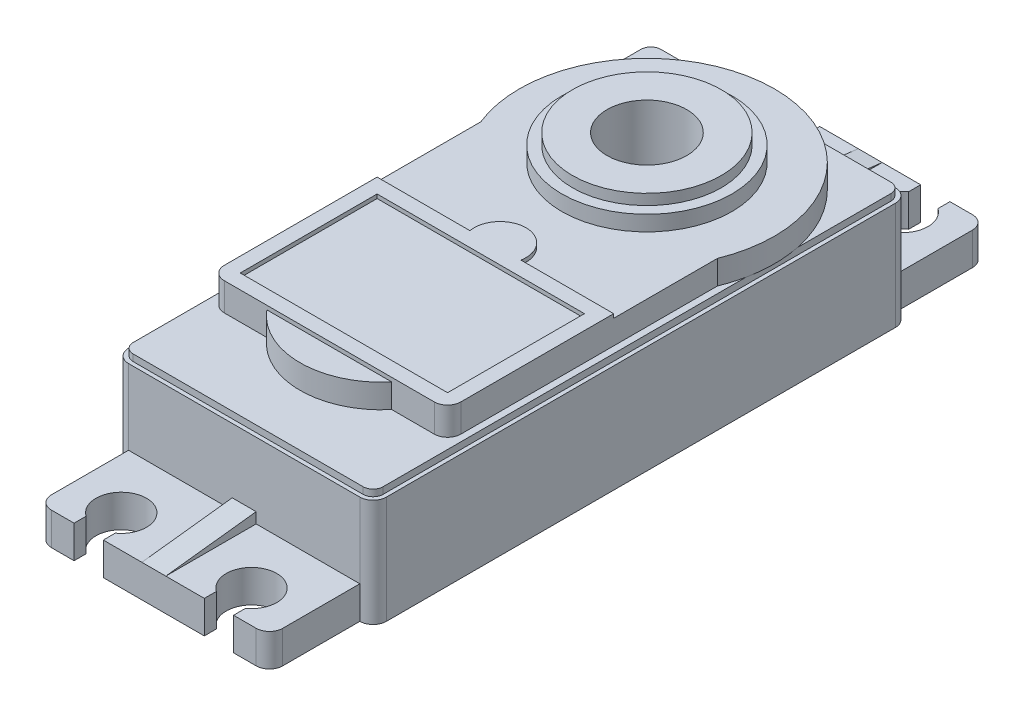
SolidWorks part; units mm, degrees
material "PC High Viscosity"
ref_plane "Front Plane" through (0, 0, 0) normal (0, 0, 1) x (1, 0, 0)
ref_plane "Top Plane" through (0, 0, 0) normal (0, 1, 0) x (1, 0, 0)
ref_plane "Right Plane" through (0, 0, 0) normal (1, 0, 0) x (0, 0, -1)
sketch "BaseS" plane through (0, 0, 0) normal (0, 1, 0) x (1, 0, 0)
  line L1 (-9.7, 20.15) -> (9.7, 20.15)
  line L2 (-9.7, 20.15) -> (-9.7, -20.15)
  line L3 (-9.7, -20.15) -> (9.7, -20.15)
  line L4 (9.7, 20.15) -> (9.7, -20.15)
  line L5 (-9.7, 20.15) -> (9.7, -20.15) construction
  line L6 (-9.7, -20.15) -> (9.7, 20.15) construction
  point P0 (0, 0)
  dimension "D1" = 19.4
  dimension "D2" = 40.3
extrude "BASE" add sketch "BaseS" along normal blind 8.6 contours L4 L3 L2 L1
sketch "ShaftHoleS" plane through (0, 8.6, 0) normal (0, 1, 0) x (1, 0, 0)
  line L0 (0, 10.15) -> (0, 20.15) construction
  line L1 (-9.7, 20.15) -> (9.7, 20.15) construction
  circle A0 centre (0, 10.15) radius 3
  dimension "D1" = 6
  dimension "D2" = 10
extrude "SHAFT HOLE" cut sketch "ShaftHoleS" against normal through all
sketch "MountingTabS" plane through (0, 0, 20.15) normal (0, 0, 1) x (1, 0, 0)
  line L0 (-9.7, 0) -> (9.7, 0) construction
  line L1 (-8.7, 2.45) -> (8.7, 2.45)
  line L2 (-8.7, 2.45) -> (-8.7, 0)
  line L3 (-8.7, 0) -> (8.7, 0)
  line L4 (8.7, 2.45) -> (8.7, 0)
  line L5 (-8.7, 2.45) -> (8.7, 0) construction
  line L6 (-8.7, 0) -> (8.7, 2.45) construction
  line L7 (9.7, 8.6) -> (9.7, 0) construction
  point P0 (0, 1.225)
  dimension "D1" = 1
  dimension "D2" = 2.45
  dimension "D3" = 17.4
extrude "MOUNTING TAB" add sketch "MountingTabS" along normal blind 6.8
sketch "MountingHoleS" plane through (0, 2.45, 0) normal (0, 1, 0) x (1, 0, 0)
  line L0 (0, -26.95) -> (0, -20.15) construction
  line L1 (-6, -26.0492) -> (-6, -26.95)
  line L2 (-6, -26.95) -> (-3.8, -26.95)
  line L3 (-3.8, -26.95) -> (-3.8, -26.0492)
  line L4 (-4.9, -24.5) -> (-4.9, -26.95) construction
  line L5 (8.7, -20.15) -> (-8.7, -20.15) construction
  line L6 (8.7, -26.95) -> (-8.7, -26.95) construction
  line L8 (-9.7, 20.15) -> (-9.7, -20.15) construction
  arc A0 (-3.8, -26.0492) -> (-6, -26.0492) centre (-4.9, -24.5) ccw
  point P16 (-9.7, 0)
  dimension "D1" = 3.8
  dimension "D2" = 4.9
  dimension "D3" = 2.2
  dimension "D4" = 24.5
extrude "MOUNTING HOLE" cut sketch "MountingHoleS" against normal through all
mirror "MH M" about plane through (0, 0, 0) normal (1, 0, 0) of "MOUNTING HOLE"
sketch "BottomAlignHoleS" plane through (0, 0, 0) normal (0, -1, 0) x (1, 0, 0)
  line L0 (0, 26.95) -> (0, 24.95) construction
  line L1 (-3.8, 26.95) -> (3.8, 26.95) construction
  circle A0 centre (0, 24.95) radius 0.7
  dimension "D1" = 1.4
  dimension "D2" = 2
extrude "BOTTOM ALIGN HOLE" cut sketch "BottomAlignHoleS" against normal blind 0.5
sketch "TriangularTabS" plane through (0, 0, 0) normal (1, 0, 0) x (0, 0, -1)
  line L0 (-20.15, 2.45) -> (-26.95, 2.45)
  line L1 (-26.95, 2.45) -> (-20.15, 3.25)
  line L2 (-20.15, 3.25) -> (-20.15, 2.45)
  line L3 (-26.0492, 2.45) -> (-26.95, 2.45) construction
  dimension "D1" = 0.8
extrude "TRIANGULAR TAB" add sketch "TriangularTabS" along normal mid plane 1.8
mirror "MOUNTING TAB FEATURES M" about plane through (0, 0, 0) normal (0, 0, 1) of "TRIANGULAR TAB", "BOTTOM ALIGN HOLE", "MH M", "MOUNTING HOLE", "MOUNTING TAB"
sketch "BaseTopBodyS" plane through (0, 8.6, 0) normal (0, 1, 0) x (1, 0, 0)
  line L0 (-8.9, -13.7486) -> (8.9, -13.7486)
  line L1 (8.9, -13.7486) -> (8.9, 6.5514)
  line L2 (-8.9, -13.7486) -> (-8.9, 6.5514)
  line L3 (0, -13.7486) -> (0, 0) construction
  arc A0 (8.9, 6.5514) -> (-8.9, 6.5514) centre (0, 10.15) ccw
  circle A1 centre (0, 10.15) radius 3
  circle A2 centre (0, 10.15) radius 3 construction
  dimension "D1" = 19.2
  dimension "D2" = 17.8
  dimension "D3" = 20.3
extrude "BASE TOP BODY" add sketch "BaseTopBodyS" along normal blind 1.8
sketch "PartCircleS" plane through (0, 8.6, 0) normal (0, 1, 0) x (1, 0, 0)
  line L0 (-4.7, -13.7486) -> (4.7, -13.7486) construction
  line L1 (0, -13.7486) -> (0, -15.9486) construction
  line L2 (-4.7, -13.7486) -> (4.7, -13.7486)
  line L3 (-8.9, -13.7486) -> (8.9, -13.7486) construction
  arc A0 (-4.7, -13.7486) -> (4.7, -13.7486) centre (0, -9.8282) ccw
  dimension "D1" = 2.2
  dimension "D2" = 9.4
extrude "PART CIRCLE" add sketch "PartCircleS" along normal up to surface (1.8 mm away) up to face at (0, 10.4, 0.299)
sketch "TopBodyCylinder1" plane through (0, 10.4, 0) normal (0, 1, 0) x (1, 0, 0)
  circle A0 centre (0, 10.15) radius 3
  circle A1 centre (0, 10.15) radius 6.4
  circle A2 centre (0, 10.15) radius 3 construction
  dimension "D1" = 12.8
extrude "TOP BODY CYLINDER 1" add sketch "TopBodyCylinder1" along normal blind 1.15
sketch "TopBodyCylinder2" plane through (0, 11.55, 0) normal (0, 1, 0) x (1, 0, 0)
  circle A0 centre (0, 10.15) radius 5.6
  circle A1 centre (0, 10.15) radius 6.4 construction
  circle A2 centre (0, 10.15) radius 3 construction
  circle A3 centre (0, 10.15) radius 3
  dimension "D1" = 0.8
  dimension "D2" = 11.2
extrude "TOB BODY CYLINDER 2" add sketch "TopBodyCylinder2" along normal blind 0.8
sketch "TopBodyLabelNest" plane through (0, 10.4, 0) normal (0, 1, 0) x (1, 0, 0)
  line L0 (-8.9, -1.2486) -> (8.9, -1.2486)
  line L1 (-8.9, -1.2486) -> (-8.9, -13.7486)
  line L2 (-8.9, -13.7486) -> (8.9, -13.7486)
  line L3 (8.9, -1.2486) -> (8.9, -13.7486)
  line L4 (-8.9, -1.2486) -> (8.9, -13.7486) construction
  line L5 (-8.9, -13.7486) -> (8.9, -1.2486) construction
  line L6 (-7.8, -2.3486) -> (7.8, -2.3486)
  line L7 (-7.8, -2.3486) -> (-7.8, -12.6486)
  line L8 (-7.8, -12.6486) -> (7.8, -12.6486)
  line L9 (7.8, -2.3486) -> (7.8, -12.6486)
  line L10 (-7.8, -2.3486) -> (7.8, -12.6486) construction
  line L11 (-7.8, -12.6486) -> (7.8, -2.3486) construction
  line L12 (8.9, -13.7486) -> (8.9, 6.5514) construction
  line L13 (0, -2.3486) -> (0, -1.2486) construction
  line L14 (-7.8, -7.4986) -> (-8.9, -7.4986) construction
  point P0 (0, -7.4986)
  point P5 (0, -7.4986)
  dimension "D1" = 12.5
  dimension "D2" = 1.1
extrude "TOP BODY LABEL NEST" add sketch "TopBodyLabelNest" along normal blind 0.3
sketch "PartCircle2S" plane through (0, 10.4, 0) normal (0, 1, 0) x (1, 0, 0)
  line L0 (1.3038, -2.3486) -> (-1.3038, -2.3486)
  line L1 (0, -2.3486) -> (0, 3.75) construction
  line L2 (0, 1.0514) -> (0, 3.75) construction
  line L3 (7.8, -2.3486) -> (-7.8, -2.3486) construction
  arc A0 (1.3038, -2.3486) -> (-1.3038, -2.3486) centre (0, -0.8986) ccw
  circle A1 centre (0, 10.15) radius 6.4 construction
  dimension "D2" = 1.95
  dimension "D1" = 3.4
extrude "PART CIRCLE 2" add sketch "PartCircle2S" along normal up to surface (0.3 mm away) up to face at (0, 10.7, 7.4986)
sketch "BorderCutS" plane through (0, 8.6, 0) normal (0, 1, 0) x (1, 0, 0)
  line L0 (-9.4, 19.85) -> (-9.4, -19.85)
  line L1 (-9.4, -19.85) -> (9.4, -19.85)
  line L2 (9.4, -19.85) -> (9.4, 19.85)
  line L3 (9.4, 19.85) -> (-9.4, 19.85)
  line L4 (-9.7, 20.15) -> (-9.7, -20.15)
  line L5 (-9.7, -20.15) -> (9.7, -20.15)
  line L6 (9.7, -20.15) -> (9.7, 20.15)
  line L7 (9.7, 20.15) -> (-9.7, 20.15)
  line L8 (-9.7, 0) -> (-9.4, 0) construction
  line L9 (0, -20.15) -> (0, -19.85) construction
  dimension "D1" = 0.3
extrude "BORDER CUT" cut sketch "BorderCutS" against normal blind 0.5
fillet "MAIN BODY FEATURES F" radius 1 10 edges at (8.7, 1.225, -26.95) (-8.7, 1.225, -26.95) (-9.7, 4.05, -20.15) (9.7, 4.05, -20.15) (-8.9, 9.65, 13.7486) (8.9, 9.65, 13.7486) (-9.7, 4.05, 20.15) (9.7, 4.05, 20.15) (8.7, 1.225, 26.95) (-8.7, 1.225, 26.95)
fillet "BORDER CUT F" radius 0.75 4 edges at (-9.4, 8.35, -19.85) (9.4, 8.35, -19.85) (9.4, 8.35, 19.85) (-9.4, 8.35, 19.85)
